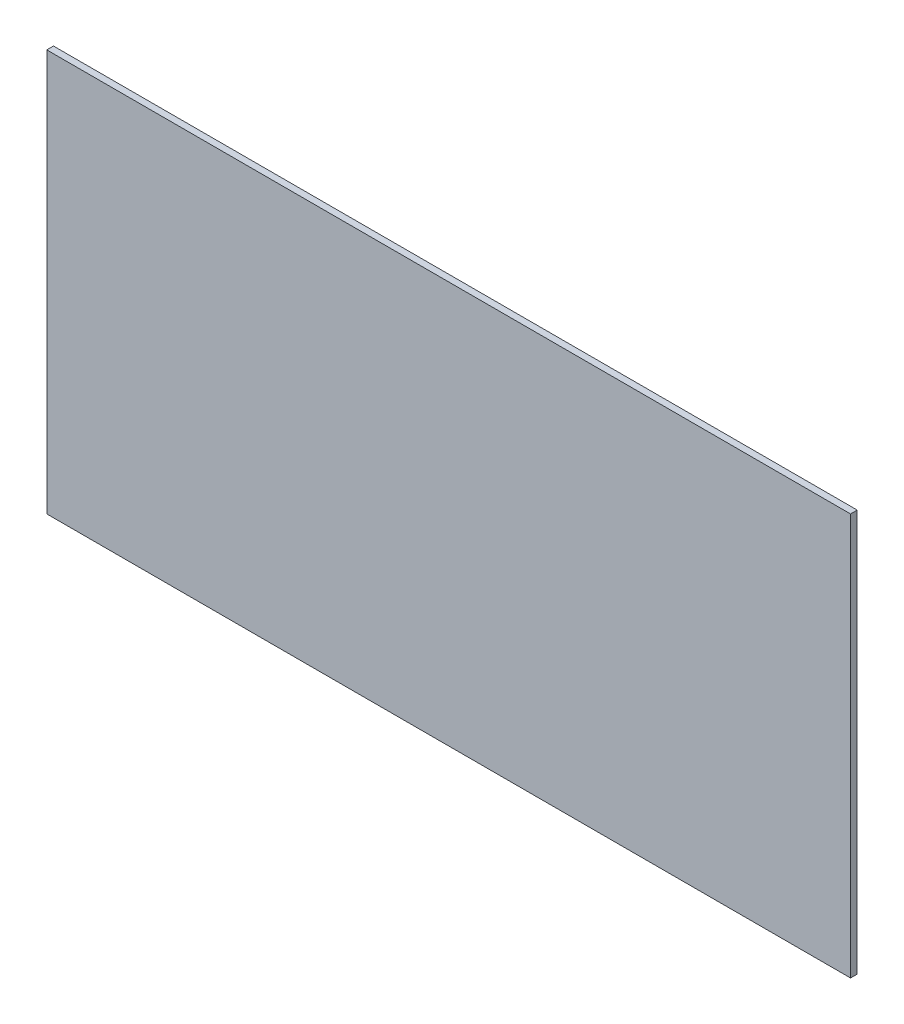
SolidWorks part; units mm, degrees
material "1060 Alloy"
ref_plane "Front Plane" through (0, 0, 0) normal (0, 0, 1) x (1, 0, 0)
ref_plane "Top Plane" through (0, 0, 0) normal (0, 1, 0) x (1, 0, 0)
ref_plane "Right Plane" through (0, 0, 0) normal (1, 0, 0) x (0, 0, -1)
sketch "Sketch1" plane through (0, 0, 0) normal (0, 0, 1) x (1, 0, 0)
  line L1 (0, 0) -> (120, 0)
  line L2 (0, 0) -> (0, 60)
  line L3 (0, 60) -> (120, 60)
  line L4 (120, 0) -> (120, 60)
  dimension "D1" = 120
  dimension "D2" = 60
base flange "Base-Flange1" sketch "Sketch1" thickness 1 reverse thickness direction no parameters "D1"=0.7366
sketch "Bend-Lines1" [suppressed] plane through (0, 0, 0) normal (0, 1, 0) x (1, 0, 0)
sketch "Bounding-Box1" [suppressed] plane through (0, 0, 0) normal (0, 1, 0) x (1, 0, 0)
sheet metal parameters "Sheet-Metal1" thickness 1 parameters "D1"=0.7366
flat pattern "Flat-Pattern1" [suppressed]
sketch "Bend-Lines2" plane through (0, 0, 0) normal (0, 1, 0) x (1, 0, 0)
sketch3d "Bounding-Box2" [suppressed]
  line L0 (0, 0, 0) -> (-120, 0, 0) construction
  line L1 (0, 60, 0) -> (-120, 60, 0) construction
  line L2 (0, 0, 0) -> (0, 60, 0) construction
  line L3 (-120, 0, 0) -> (-120, 60, 0) construction
